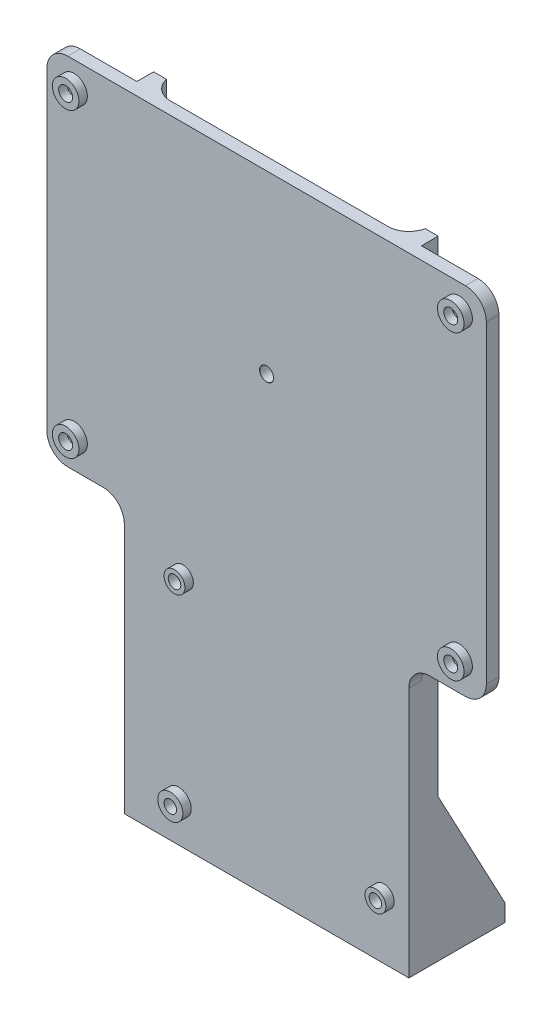
SolidWorks part; units mm, degrees
note: The reader was unsure of these and kept them because the rebuilt part matched: shared geometry of "草图4<2>".
ref_plane "前视基准面" through (0, 0, 0) normal (0, 0, 1) x (1, 0, 0)
ref_plane "上视基准面" through (0, 0, 0) normal (0, 1, 0) x (1, 0, 0)
ref_plane "右视基准面" through (0, 0, 0) normal (1, 0, 0) x (0, 0, -1)
other "Configuration Table"
sketch "草图1" plane through (0, 0, 0) normal (0, 0, 1) x (1, 0, 0)
  line L1 (-34, -32.5) -> (34, -32.5)
  line L2 (-34, -32.5) -> (-34, 32.5)
  line L3 (-34, 32.5) -> (34, 32.5)
  line L4 (34, -32.5) -> (34, 32.5)
  line L5 (-34, -32.5) -> (34, 32.5) construction
  line L6 (-34, 32.5) -> (34, -32.5) construction
  line L7 (-52.5, 117.5) -> (52.5, 117.5)
  line L8 (-52.5, 117.5) -> (-52.5, 32.5)
  line L9 (-52.5, 32.5) -> (52.5, 32.5)
  line L10 (52.5, 117.5) -> (52.5, 32.5)
  line L11 (-52.5, 117.5) -> (52.5, 32.5) construction
  line L12 (-52.5, 32.5) -> (52.5, 117.5) construction
  point P0 (0, 0)
  point P6 (0, 75)
  point P11 (0, 0)
  dimension "D1" = 68
  dimension "D2" = 65
  dimension "D3" = 105
  dimension "D4" = 85
extrude "凸台-拉伸1" add sketch "草图1" along normal blind 3 contours L10 L7 L8 L9 L3 | L1 L4 L3 L2
sketch "草图2" plane through (0, 0, 0) normal (0, 0, -1) x (-1, 0, 0)
  line L0 (52.5, 117.5) -> (-52.5, 117.5) construction
  line L1 (-34, -32.5) -> (-31, -32.5)
  line L2 (-34, -32.5) -> (-34, 117.5)
  line L3 (-34, 117.5) -> (-31, 117.5)
  line L4 (-31, -32.5) -> (-31, 117.5)
  line L6 (34, -32.5) -> (31, -32.5)
  line L7 (34, -32.5) -> (34, 117.5)
  line L8 (34, 117.5) -> (31, 117.5)
  line L9 (31, -32.5) -> (31, 117.5)
  dimension "D1" = 3
  dimension "D2" = 3
extrude "凸台-拉伸2" add sketch "草图2" along normal blind 4
sketch "草图3" plane through (0, 0, 0) normal (0, 0, -1) x (-1, 0, 0)
  line L0 (34, -32.5) -> (34, 117.5) construction
  line L1 (-34, -32.5) -> (34, -32.5)
  line L2 (-34, -32.5) -> (-34, -28.5)
  line L3 (-34, -28.5) -> (34, -28.5)
  line L4 (34, -32.5) -> (34, -28.5)
  dimension "D1" = 4
extrude "凸台-拉伸3" add sketch "草图3" along normal blind 20
sketch "草图4" plane through (34, 0, 0) normal (1, 0, 0) x (0, 0, -1)
  line L0 (4, -28.5) -> (20, -28.5)
  line L1 (20, -28.5) -> (4, 1.5)
  line L2 (4, 117.5) -> (4, -28.5) construction
  line L3 (4, 1.5) -> (4, -28.5)
  dimension "D1" = 30
extrude "凸台-拉伸4" add sketch "草图4" against normal up to surface (3 mm away) up to face at (31, 44.5, -2)
extrude "凸台-拉伸5" add sketch "草图4<2>" against normal up to surface (3 mm away) from surface
sketch "草图4<2>" plane through (34, 0, 0) normal (1, 0, 0) x (0, 0, -1) same geometry as "草图4"
sketch "草图5" plane through (0, -28.5, 0) normal (0, 1, 0) x (1, 0, 0)
  line L0 (-31, 15) -> (31, 15) construction
  line L1 (-31, 20) -> (-31, 4) construction
  line L2 (31, 4) -> (31, 20) construction
  line L3 (0, 20) -> (0, 0) construction
  line L4 (-31, 20) -> (31, 20) construction
  circle A0 centre (-17.5, 15) radius 1.65
  circle A1 centre (17.5, 15) radius 1.65
  dimension "D1" = 35
  dimension "D2" = 3.3
  dimension "D3" = 5
extrude "切除-拉伸1" cut sketch "草图5" against normal blind 20
sketch "草图6" plane through (0, 0, 3) normal (0, 0, 1) x (1, 0, 0)
  line L0 (0, 117.5) -> (0, 0) construction
  line L1 (-52.5, 117.5) -> (52.5, 117.5) construction
  line L3 (-46, 39.5) -> (46, 39.5) construction
  line L4 (-46, 39.5) -> (-46, 111.5) construction
  line L5 (-46, 111.5) -> (46, 111.5) construction
  line L6 (46, 39.5) -> (46, 111.5) construction
  line L7 (-46, 39.5) -> (46, 111.5) construction
  line L8 (-46, 111.5) -> (46, 39.5) construction
  point P5 (0, 75.5)
  point P6 (46, 111.5)
  point P7 (-46, 39.5)
  point P8 (-46, 111.5)
  point P9 (46, 39.5)
  point P19 (46, 111.5)
  point P21 (46, 39.5)
  point P23 (-46, 39.5)
  point P25 (-46, 111.5)
  dimension "D1" = 72
  dimension "D2" = 92
  dimension "D3" = 6
hole_wizard "Ø3.3 (3.3) 直径孔1" positions "草图6" profile "草图7" hole size "Ø3.3" standard "GB" end condition through all
sketch "草图7" plane through (-46, 111.5, 3) normal (1, 0, 0) x (0, -1, 0)
  line L0 (0, 0) -> (0, 23)
  line L1 (0, 23) -> (1.65, 23)
  line L2 (1.65, 23) -> (1.65, 0.021)
  line L3 (1.65, 0.021) -> (1.675, 0)
  line L5 (1.675, 0) -> (0, 0)
  line L6 (-1.65, 0.021) -> (-1.675, 0) construction
  line L11 (0, -6.35) -> (0, 107.95) construction
  dimension "通孔孔直径" = 3.3
  dimension "通孔孔深度" = 23
  dimension "近端锥形沉头孔直径" = 3.35
  dimension "近端锥形沉头孔角度" = 100
sketch "草图8" plane through (0, 0, 0) normal (0, 0, -1) x (-1, 0, 0)
  line L0 (34, 1.5) -> (34, -28.5) construction
  line L1 (31, -28.5) -> (-31, -28.5) construction
  circle A0 centre (21, -23.5) radius 1.5
  circle A1 centre (-28, -18.5) radius 1.5
  circle A2 centre (20, 23.5) radius 1.5
  dimension "D3" = 3
  dimension "D4" = 49
  dimension "D5" = 5
  dimension "D6" = 3
  dimension "D7" = 47
  dimension "D8" = 1
  dimension "D9" = 3
  dimension "D1" = 13
  dimension "D2" = 5
extrude "切除-拉伸2" cut sketch "草图8" against normal through all
sketch "草图9" plane through (0, 0, 3) normal (0, 0, 1) x (1, 0, 0)
  circle A0 centre (28, -18.5) radius 1.5 construction
  circle A1 centre (-21, -23.5) radius 1.5 construction
  circle A2 centre (-20, 23.5) radius 1.5 construction
  circle A3 centre (46, 39.5) radius 1.675 construction
  circle A4 centre (46, 111.5) radius 1.675 construction
  circle A5 centre (-46, 39.5) radius 1.675 construction
  circle A6 centre (-46, 111.5) radius 1.675 construction
  circle A7 centre (28, -18.5) radius 1.5
  circle A8 centre (-21, -23.5) radius 1.5
  circle A9 centre (-20, 23.5) radius 1.5
  circle A10 centre (46, 39.5) radius 1.675
  circle A11 centre (46, 111.5) radius 1.675
  circle A12 centre (-46, 39.5) radius 1.675
  circle A13 centre (-46, 111.5) radius 1.675
  circle A14 centre (-46, 111.5) radius 3.175
  circle A15 centre (46, 111.5) radius 3.175
  circle A16 centre (46, 39.5) radius 3.175
  circle A17 centre (-46, 39.5) radius 3.175
  circle A19 centre (-21, -23.5) radius 3
  circle A22 centre (-20, 23.5) radius 2.5
  circle A23 centre (28, -18.5) radius 2.5
  dimension "D2" = 1
  dimension "D3" = 1
  dimension "D1" = 1.5
extrude "凸台-拉伸6" add sketch "草图9" along normal blind 2 separate body
fillet "圆角1" radius 5 8 edges at (-31, 44.5, 0) (31, 44.5, 0) (52.5, 32.5, 1.5) (34, 32.5, 1.5) (-34, 32.5, 1.5) (-52.5, 32.5, 1.5) (-52.5, 117.5, 1.5) (52.5, 117.5, 1.5)
